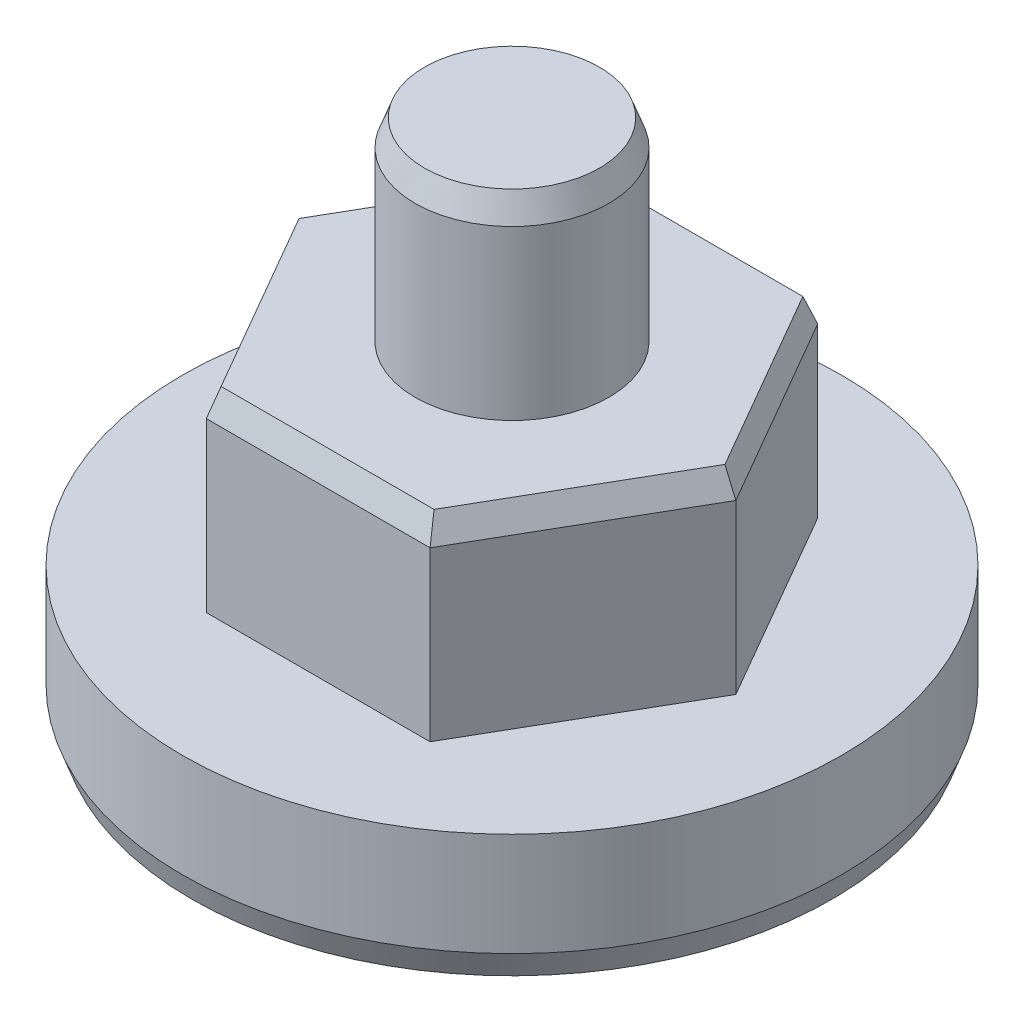
SolidWorks part; units mm, degrees
ref_plane "Front Plane" through (0, 0, 0) normal (0, 0, 1) x (1, 0, 0)
ref_plane "Top Plane" through (0, 0, 0) normal (0, 1, 0) x (1, 0, 0)
ref_plane "Right Plane" through (0, 0, 0) normal (1, 0, 0) x (0, 0, -1)
sketch "Sketch1" plane through (0, 0, 0) normal (0, 1, 0) x (1, 0, 0)
  circle A0 centre (0, 0) radius 25.5
  dimension "D1" = 51
extrude "Boss-Extrude1" add sketch "Sketch1" along normal mid plane 10
sketch "Sketch2" plane through (0, 5, 0) normal (0, 1, 0) x (1, 0, 0)
  line L1 (-17.3205, 0) -> (-8.6603, -15)
  line L2 (-8.6603, -15) -> (8.6603, -15)
  line L3 (8.6603, -15) -> (17.3205, 0)
  line L4 (17.3205, 0) -> (8.6603, 15)
  line L5 (8.6603, 15) -> (-8.6603, 15)
  line L6 (-8.6603, 15) -> (-17.3205, 0)
  circle A0 centre (0, 0) radius 15 construction
  dimension "D1" = 30
extrude "Boss-Extrude2" add sketch "Sketch2" along normal blind 15
sketch "Sketch3" plane through (0, 20, 0) normal (0, 1, 0) x (1, 0, 0)
  circle A0 centre (0, 0) radius 7.5
  dimension "D1" = 15
extrude "Boss-Extrude3" add sketch "Sketch3" along normal blind 15
chamfer "Chamfer1" distance 2 angle 20 6 edges at (-12.9904, 20, -7.5) (-12.9904, 20, 7.5) (0, 20, 15) (12.9904, 20, 7.5) (12.9904, 20, -7.5) (0, 20, -15) first distance on face at (-12.9904, 12.5, -7.5) first distance on face at (-12.9904, 12.5, 7.5) first distance on face at (0, 12.5, 15) first distance on face at (12.9904, 12.5, 7.5) first distance on face at (12.9904, 12.5, -7.5) first distance on face at (0, 12.5, -15)
chamfer "Chamfer2" distance 2 angle 20 1 edges at (0, -5, 25.5) first distance on face at (0, 5, 25.5)
chamfer "Chamfer3" distance 2 angle 20 1 edges at (0, 35, 7.5) first distance on face at (0, 35, 7.5)
